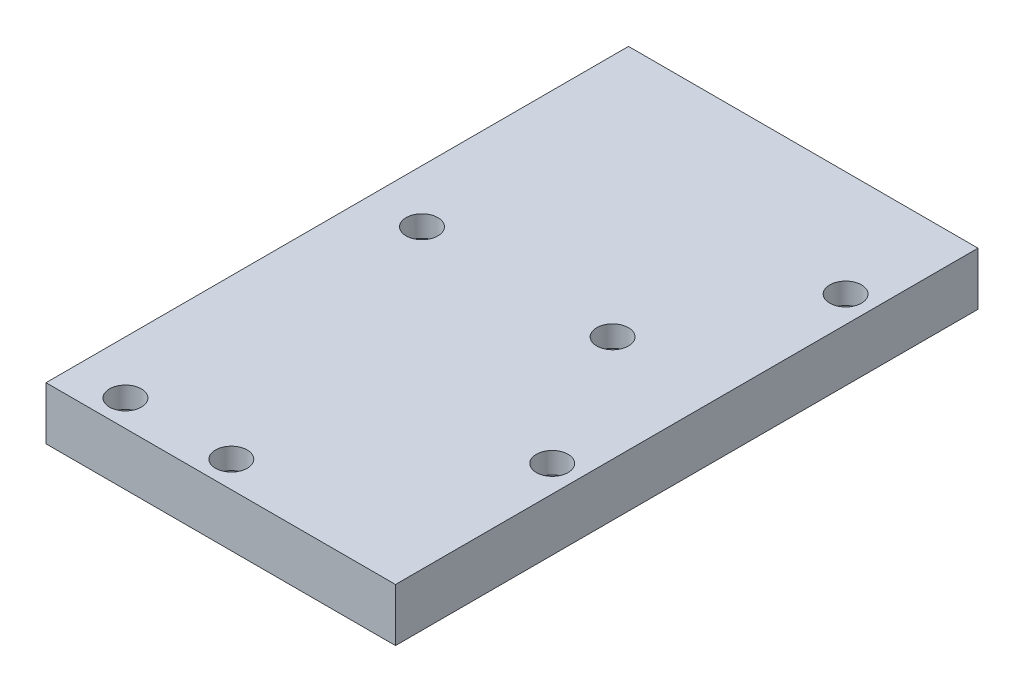
SolidWorks part; units mm, degrees
other "标注1"
sketch "草图3" plane through (0, 5, 29.5) normal (-0.6417, 0.7662, 0.0339) x (0.7661, 0.6384, 0.0747)
ref_plane "前视基准面" through (0, 0, 0) normal (0, 0, 1) x (1, 0, 0)
ref_plane "上视基准面" through (0, 0, 0) normal (0, 1, 0) x (1, 0, 0)
ref_plane "右视基准面" through (0, 0, 0) normal (1, 0, 0) x (0, 0, -1)
other "Configuration Table"
sketch "草图1" plane through (0, 0, 0) normal (0, 1, 0) x (1, 0, 0)
  line L33 (-28, -55) -> (0, -55)
  line L34 (-28, -55) -> (-28, 0)
  line L36 (0, -55) -> (0, 0)
  line L37 (-28, 0) -> (0, 0)
  circle A12 centre (-23, -24.5) radius 1.5
  circle A13 centre (-23, -24.5) radius 2.25
  circle A14 centre (-5, -24.5) radius 1.5
  circle A15 centre (-5, -24.5) radius 2.25
  circle A16 centre (-13, -52.5) radius 1.5
  circle A17 centre (-13, -52.5) radius 2.25
  circle A22 centre (2.5, -37.702) radius 1.5
  circle A23 centre (2.5, -37.702) radius 2.25
  circle A26 centre (-23, -52.5) radius 1.5
  circle A27 centre (-23, -52.5) radius 2.25
  circle A28 centre (2.5, -10) radius 1.5
  circle A29 centre (2.5, -10) radius 2.25
  dimension "D1" = 28
  dimension "D2" = 55
  dimension "D3" = 3
  dimension "D4" = 4.5
extrude "凸台-拉伸1" add sketch "草图1" along normal blind 5 contours L34 | L36 L37 L34 L33 | A14 | A12 | A16 | A26
sketch "草图4" plane through (-28, 0, 0) normal (-1, 0, 0) x (0, 0, 1)
  line L0 (0, 5) -> (0, 0) construction
  line L1 (55, 5) -> (55, 0) construction
  line L2 (0, 2.5) -> (55, 2.5)
  circle A0 centre (10, 2.5) radius 0.85
  circle A1 centre (45, 2.5) radius 0.85
  dimension "D1" = 1.7
  dimension "D2" = 10
  dimension "D3" = 10
extrude "切除-拉伸1" cut sketch "草图4" against normal blind 4 and the other way through all contours A0 | A1
sketch "草图5" plane through (0, 0, 0) normal (1, 0, 0) x (0, 0, -1)
  line L1 (-55, 5) -> (0, 5)
  line L2 (-55, 5) -> (-55, 0)
  line L3 (-55, 0) -> (0, 0)
  line L4 (0, 5) -> (0, 0)
extrude "凸台-拉伸2" add sketch "草图5" along normal blind 5
extrude "切除-拉伸2" cut sketch "草图1<22>" along normal through all contours A28 | A22
sketch "草图1<22>" plane through (0, 0, 0) normal (0, 1, 0) x (1, 0, 0) same geometry as "草图1"
extrude "切除-拉伸3" cut sketch "草图1<23>" along normal offset from surface (3 mm away) 2 contours A29 | A15 | A23 | A17 | A27 | A13 up to face at (2.5, 5, 11.5)
sketch "草图1<23>" plane through (0, 0, 0) normal (0, 1, 0) x (1, 0, 0) same geometry as "草图1"
